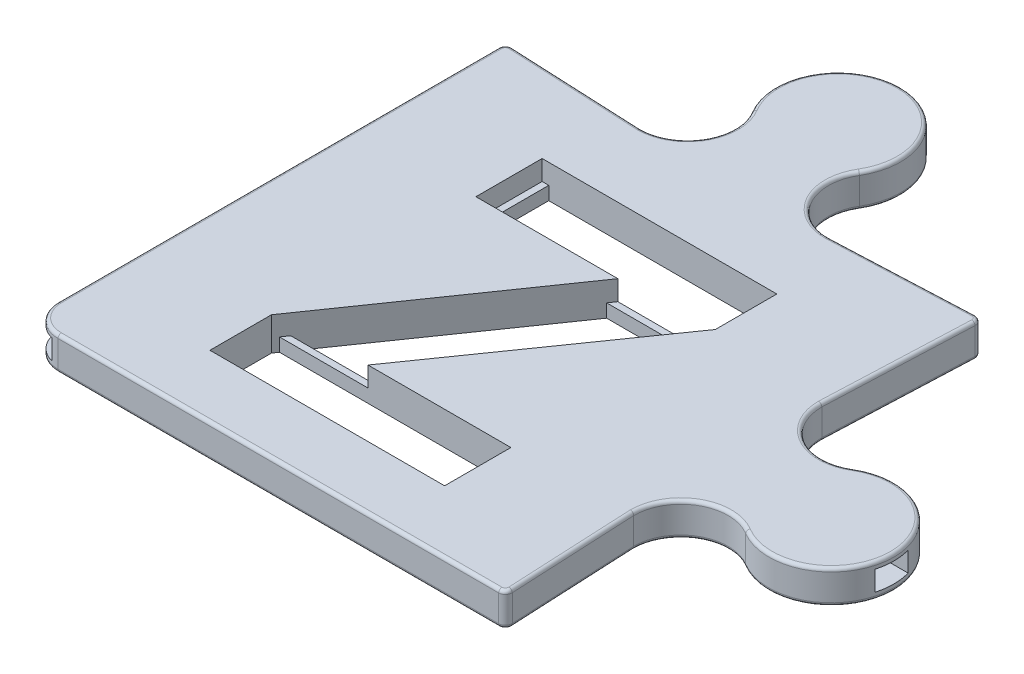
SolidWorks part; units mm, degrees
ref_plane "Front Plane" through (0, 0, 0) normal (0, 0, 1) x (1, 0, 0)
ref_plane "Top Plane" through (0, 0, 0) normal (0, 1, 0) x (1, 0, 0)
ref_plane "Right Plane" through (0, 0, 0) normal (1, 0, 0) x (0, 0, -1)
sketch "Sketch1" plane through (0, 0, 0) normal (0, 1, 0) x (1, 0, 0)
  line L0 (-31, -36) -> (37, -36) construction
  line L1 (-36, 37) -> (-36, -31) construction
  line L2 (-14.1421, 36) -> (-36, 37) construction
  line L3 (37, 37) -> (14.1421, 36) construction
  line L4 (36, 13.1421) -> (37, 37) construction
  line L5 (37, -36) -> (36, -15.1421) construction
  line L6 (-35.4, 36.3719) -> (-35.4, -31)
  line L7 (-36, 36) -> (36, 36) construction
  line L8 (-36, 36) -> (-36, -36) construction
  line L9 (-36, -36) -> (36, -36) construction
  line L10 (36, 36) -> (36, -36) construction
  line L11 (-31, -35.4) -> (36.3705, -35.4)
  line L12 (36.3705, -35.4) -> (35.4, -15.1568)
  line L13 (35.4, 13.155) -> (36.3732, 36.372)
  line L14 (36.3732, 36.372) -> (14.1555, 35.4)
  line L15 (-14.1562, 35.4) -> (-35.4, 36.3719)
  line L16 (-30, -24) -> (30, -24) construction
  line L17 (-30, 29) -> (30, 29) construction
  line L18 (-30, 29) -> (-30, -31) construction
  line L19 (-30, -31) -> (30, -31) construction
  line L20 (30, 29) -> (30, -31) construction
  line L21 (-30, 24) -> (30, 24) construction
  line L22 (-30, 24) -> (-30, -26) construction
  line L23 (-30, -26) -> (30, -26) construction
  line L24 (30, 24) -> (30, -26) construction
  arc A0 (-36, -31) -> (-31, -36) centre (-31, -31) ccw construction
  arc A1 (-14.1421, 36) -> (-8.571, 45.8485) centre (-14.1421, 42.5) ccw construction
  arc A2 (8.571, 45.8485) -> (-8.571, 45.8485) centre (0, 51) ccw construction
  arc A3 (8.571, 45.8485) -> (14.1421, 36) centre (14.1421, 42.5) ccw construction
  arc A4 (36, 13.1421) -> (45.8485, 7.571) centre (42.5, 13.1421) ccw construction
  arc A5 (45.8485, -9.571) -> (45.8485, 7.571) centre (51, -1) ccw construction
  arc A6 (45.8485, -9.571) -> (36, -15.1421) centre (42.5, -15.1421) ccw construction
  arc A7 (-35.4, -31) -> (-31, -35.4) centre (-31, -31) ccw
  arc A8 (46.1576, -9.0567) -> (35.4, -15.1568) centre (42.5, -15.1421) ccw
  arc A9 (46.1576, -9.0567) -> (46.1576, 7.0567) centre (51, -1) ccw
  arc A10 (35.4, 13.155) -> (46.1576, 7.0567) centre (42.5, 13.1421) ccw
  arc A11 (8.0567, 46.1576) -> (14.1555, 35.4) centre (14.1421, 42.5) ccw
  arc A12 (8.0567, 46.1576) -> (-8.0567, 46.1576) centre (0, 51) ccw
  arc A13 (-14.1562, 35.4) -> (-8.0567, 46.1576) centre (-14.1421, 42.5) ccw
  point P32 (36, 0)
  point P34 (0, 36)
  dimension "D5" = 6.5
  dimension "D6" = 10
  dimension "D7" = 6.5
  dimension "D13" = 5
  dimension "D9" = 10
  dimension "D11" = 6.5
  dimension "D12" = 6.5
  dimension "D1" = 72
  dimension "D2" = 1
  dimension "D3" = 1
  dimension "D4" = 15
  dimension "D8" = 1
  dimension "D10" = 35
  dimension "D14" = 15
  dimension "D15" = 36
  dimension "D16" = 1
  dimension "D18" = 60
  dimension "D19" = 60
  dimension "D20" = 5
  dimension "D21" = 6
  dimension "D22" = 5
  dimension "D23" = 50
  dimension "D24" = 2
  dimension "D17" = 0.6
extrude "Boss-Extrude1" add sketch "Sketch1" along normal blind 5
sketch "Sketch6" plane through (0, 0, 0) normal (0, -1, 0) x (1, 0, 0)
  line L0 (-35.4, -36.3719) -> (-35.4, 31) construction
  line L1 (-35.4, 17.9) -> (-27.4, 17.9)
  line L2 (-35.4, 17.9) -> (-35.4, -16.1)
  line L3 (-35.4, -16.1) -> (-27.4, -16.1)
  line L4 (-27.4, 17.9) -> (-27.4, -16.1)
  line L5 (-31, 35.4) -> (36.3705, 35.4) construction
  line L6 (-35.4, 14.65) -> (-30.4, 14.65)
  line L7 (-35.4, 14.65) -> (-35.4, -12.85)
  line L8 (-35.4, -12.85) -> (-30.4, -12.85)
  line L9 (-30.4, 14.65) -> (-30.4, -12.85)
  point P15 (-27.4, 0.9)
  point P16 (-30.4, 0.9)
  line M28 (-35.4, 31) -> (-35.4, -36.3719)
  dimension "D1" = 8
  dimension "D2" = 20.75
  dimension "D3" = 27.5
  dimension "D4" = 5
  dimension "D5" = 34
extrude "Cut-Extrude3" cut sketch "Sketch6" against normal blind 3 from offset 1 contours L6 L9 L8 L3 L4 L1 M28 | L9 L6 L2 L8 region at (-29.8665, 0, 0.9) region at (-32.9, 0, 0.9) offset against normal yes
extrude "Cut-Extrude4" cut sketch "Sketch6<3>" against normal up to next contours L9 L6 L2 L8 region at (-32.9, 0, 0.9)
sketch "Sketch6<3>" plane through (0, 0, 0) normal (0, -1, 0) x (1, 0, 0) same geometry as "Sketch6"
sketch "Sketch8" plane through (0, 0, 0) normal (0, -1, 0) x (1, 0, 0)
  line L1 (-2.5, -51.4) -> (2.5, -51.4)
  line L2 (-2.5, -51.4) -> (-2.5, -60.4)
  line L3 (-2.5, -60.4) -> (2.5, -60.4)
  line L4 (2.5, -51.4) -> (2.5, -60.4)
  line L5 (51.4, 3.5) -> (60.4, 3.5)
  line L6 (51.4, 3.5) -> (51.4, -1.5)
  line L7 (51.4, -1.5) -> (60.4, -1.5)
  line L8 (60.4, 3.5) -> (60.4, -1.5)
  arc A0 (-8.0567, -46.1576) -> (8.0567, -46.1576) centre (0, -51) ccw construction
  arc A1 (46.1576, -7.0567) -> (46.1576, 9.0567) centre (51, 1) ccw construction
  point P4 (0, -60.4)
  point P13 (60.4, 1)
  dimension "D1" = 5
  dimension "D2" = 9
  dimension "D3" = 5
  dimension "D4" = 9
extrude "Cut-Extrude5" cut sketch "Sketch8" against normal blind 3 from offset 1 offset against normal yes
sketch "Sketch9" plane through (0, 0, 0) normal (0, -1, 0) x (1, 0, 0)
  line L0 (-31, 35.4) -> (36.3705, 35.4) construction
  line L1 (-35.4, 14.65) -> (-35.4, 31) construction
  line L2 (-31.7636, 35.3332) -> (-35.4, 31) construction
  line L3 (-33.2571, 29.735) -> (-30.0429, 33.565) construction
  line L4 (-30.0429, 33.565) -> (-33.2571, 29.735) construction
  line L5 (-30.0429, 33.565) -> (-32.7119, 35.8048)
  line L6 (-33.2571, 29.735) -> (-35.926, 31.9747)
  line L7 (-32.7119, 35.8048) -> (-35.926, 31.9747)
  circle A0 centre (-31.65, 31.65) radius 2.5
  arc A1 (-31, 35.4) -> (-35.4, 31) centre (-31, 31) ccw construction
  arc M41 (-31, 35.4) -> (-35.4, 31) centre (-31, 31) ccw
  dimension "D1" = 5
  dimension "D3" = 3.75
  dimension "D4" = 5.6569
  dimension "D2" = 3.75
extrude "Cut-Extrude6" cut sketch "Sketch9" against normal blind 3 from offset 1 contours A0 L5 L6 M41 | A0 L5 region at (-33.6239, 0, 33.3064) region at (-31.65, 0, 31.65) offset against normal yes
sketch "Sketch11" plane through (-35.4, 0, 0) normal (-1, 0, 0) x (0, 0, 1)
  line L0 (-13.155, 0) -> (-36.372, 0) construction
  line L1 (-25.1, 3) -> (-19.1, 3)
  line L2 (-25.1, 3) -> (-25.1, 1.5)
  line L3 (-25.1, 1.5) -> (-19.1, 1.5)
  line L4 (-19.1, 3) -> (-19.1, 1.5)
  line L5 (-16.1, 4) -> (-16.1, 1) construction
  line L6 (35.4, 0) -> (15.1568, 0) construction
  line L7 (20.9, 3) -> (26.9, 3)
  line L8 (20.9, 3) -> (20.9, 1.5)
  line L9 (20.9, 1.5) -> (26.9, 1.5)
  line L10 (26.9, 3) -> (26.9, 1.5)
  line L12 (17.9, 4) -> (17.9, 1) construction
  dimension "D1" = 3
  dimension "D2" = 1.5
  dimension "D3" = 3
  dimension "D4" = 6
  dimension "D5" = 3
  dimension "D6" = 1.5
  dimension "D7" = 6
  dimension "D8" = 3
fillet "Fillet1" radius 0.5 17 edges at (-35.4, 0, 22.825) (-34.1113, 0, 34.1113) (2.6853, 0, 35.4) (35.8853, 0, 25.2784) (38.9978, 0, 8.966) (60.4, 0, 1) (38.9986, 0, -6.9655) (35.8866, 0, -24.7635) (25.2643, 0, -35.886) (7.9657, 0, -38.9984) (0, 0, -60.4) (-7.9658, 0, -38.9981) (-24.7781, 0, -35.886) (-35.4, 0, -24.611) (-32.9, 0, -12.85) (-30.4, 0, 0.9) (-32.9, 0, 14.65)
fillet "Fillet2" radius 0.5 13 edges at (-7.9658, 5, -38.9981) (0, 5, -60.4) (7.9657, 5, -38.9984) (25.2643, 5, -35.886) (35.8866, 5, -24.7635) (38.9986, 5, -6.9655) (60.4, 5, 1) (38.9978, 5, 8.966) (35.8853, 5, 25.2784) (2.6853, 5, 35.4) (-34.1113, 5, 34.1113) (-35.4, 5, -2.686) (-24.7781, 5, -35.886)
fillet "Fillet3" radius 1 9 edges at (36.2202, 0.1464, -36.2187) (36.2202, 4.8536, -36.2187) (36.3732, 2.5, -36.372) (-35.2536, 0.1464, -36.2186) (-35.2536, 4.8536, -36.2186) (36.2169, 0.1464, 35.2536) (36.2169, 4.8536, 35.2536) (36.3705, 2.5, 35.4) (-35.4, 2.5, -36.3719)
extrude "Cut-Extrude9" cut sketch "Sketch11" against normal blind 3
chamfer "Chamfer1" distance 1 angle 50 2 edges at (-35.4, 1.5, 23.9) (-35.4, 1.5, -22.1) first distance on face at (-35.4, 2.25, -22.1)
sketch "Sketch12" plane through (0, 5, 0) normal (0, 1, 0) x (1, 0, 0)
  text T0 "Z" font "Poppins" height 50
extrude "Cut-Extrude10" cut sketch "Sketch12" against normal through all
sketch "Sketch13" plane through (0, 0, 0) normal (0, -1, 0) x (1, 0, 0)
  line L0 (-17.5392, -24) -> (17.7865, -24) construction
  line L1 (-17.5392, -14.035) -> (-16.5392, -14.035)
  line L2 (-17.5392, -14.035) -> (-17.5392, -24)
  line L3 (-17.5392, -24) -> (-16.5392, -24)
  line L4 (-16.5392, -14.035) -> (-16.5392, -24)
  line L5 (-17.5392, 16.7358) -> (3.8232, -14.035) construction
  line L6 (3.1289, -13.035) -> (17.2895, -13.035)
  line L7 (3.1289, -13.035) -> (3.1289, -14.035)
  line L8 (3.1289, -14.035) -> (17.2895, -14.035)
  line L9 (17.2895, -13.035) -> (17.2895, -14.035)
  line L10 (17.7865, -14.7461) -> (-3.7201, 16.0247) construction
  line L11 (-3.7201, 16.0247) -> (17.7865, 16.0247) construction
  line L12 (-3.0212, 15.0247) -> (-17.0455, 15.0247)
  line L13 (-3.0212, 15.0247) -> (-3.0212, 16.0247)
  line L14 (-3.0212, 16.0247) -> (-17.0455, 16.0247)
  line L15 (-17.0455, 15.0247) -> (-17.0455, 16.0247)
  line L16 (17.7865, 26) -> (16.7865, 26)
  line L17 (17.7865, 26) -> (17.7865, 16.0247)
  line L18 (17.7865, 16.0247) -> (16.7865, 16.0247)
  line L19 (16.7865, 26) -> (16.7865, 16.0247)
  line L20 (3.8232, -14.035) -> (-17.5392, -14.035) construction
  dimension "D1" = 1
  dimension "D2" = 1
  dimension "D3" = 1
  dimension "D4" = 1
extrude "Boss-Extrude2" add sketch "Sketch13" against normal blind 2
